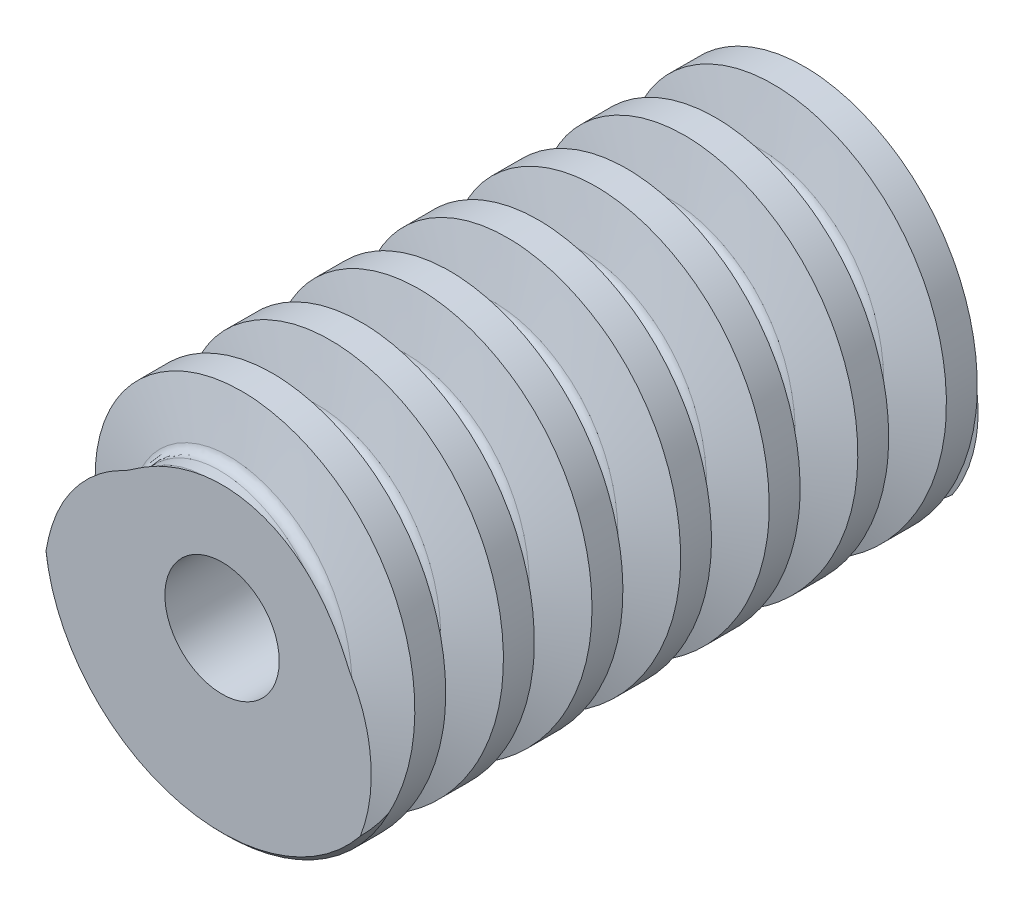
SolidWorks part; units mm, degrees
note: '?' marks a value the reader was unsure of.
material "ABS"
ref_plane "Front Plane" through (0, 0, 0) normal (0, 0, 1) x (1, 0, 0)
ref_plane "Top Plane" through (0, 0, 0) normal (0, 1, 0) x (1, 0, 0)
ref_plane "Right Plane" through (0, 0, 0) normal (1, 0, 0) x (0, 0, -1)
ref_axis "Axis1" through (0, 0, -18.5265) along (0, 0, 1)?
sketch "Worm-BaseSketch" plane through (0, 0, 0) normal (1, 0, 0) x (0, 0, -1)
  line L0 (-12.8587, 0) -> (8.7312, 0)
  line L1 (8.7312, 0) -> (8.7313, 6.2018)
  line L2 (8.7313, 6.2018) -> (8.5831, 6.35)
  line L3 (8.5831, 6.35) -> (-12.7106, 6.35)
  line L4 (-12.7106, 6.35) -> (-12.8587, 6.2018)
  line L5 (-12.8587, 6.2018) -> (-12.8587, 0)
  line L6 (-17.4625, 0) -> (17.4625, 0) construction
  dimension "Hub Surface" = 8.7313
  dimension "Chamfer (1)" = 0.1482
  dimension "Chamfer (2)" = 0.1482
  dimension "OD" = 6.35
  dimension "Chamfer (3)" = 0.1482
  dimension "Chamfer (4)" = 0.1482
  dimension "Worm Length" = 21.59
revolve "24.0 Diametral Pitch, Fine Pitch Involute 14.5 deg" add sketch "Worm-BaseSketch" angle 360 about L6
ref_plane "Plane1" through (0, 0, 15.24) normal (0, 0, 1) x (1, 0, 0)
sketch "Sketch2" plane through (0, 0, 15.24) normal (0, 0, 1) x (1, 0, 0)
  circle A0 centre (0, 0) radius 6.35
  dimension "D1" = 12.7
curve "Helix/Spiral1" pitch 3.0988 height 27.8892 turns 9
sketch "Tooth-Sketch" plane through (0, 0, 0) normal (0, 1, 0) x (1, 0, 0)
  line L0 (6.985, -9.2196) -> (6.985, -11.5677)
  line L1 (6.985, -11.5677) -> (4.6054, -10.9501)
  line L2 (4.3434, -10.6114) -> (4.3434, -10.176)
  line L3 (4.6054, -9.8373) -> (6.985, -9.2196)
  line L5 (0, -6.985) -> (0, 6.985) construction
  arc A0 (4.3434, -10.6114) -> (4.6054, -10.9501) centre (4.6934, -10.6114) ccw
  arc A1 (4.6054, -9.8373) -> (4.3434, -10.176) centre (4.6934, -10.176) ccw
  dimension "D1" = 0.35
  dimension "D2" = 0.35
  dimension "D3" = 6.985
sweep "Tooth-Cut-Sweep RH, PD: 1.1667in" cut profiles "Tooth-Sketch" path "Helix/Spiral1"
sketch "Sketch3" plane through (0, 0, 12.8587) normal (0, 0, 1) x (1, 0, 0)
  circle A0 centre (0, 0) radius 2
  dimension "D1" = 4
extrude "Cut-Extrude1" cut sketch "Sketch3" against normal through all
sketch "Sketch5" plane through (0, 0, 0) normal (0, 1, 0) x (1, 0, 0)
  line L0 (-10.4415, 0) -> (12.9723, 0) construction
ref_plane "Plane2" through (0, 0, 0) normal (0, -0.9882, 0.153) x (1, 0, 0)
